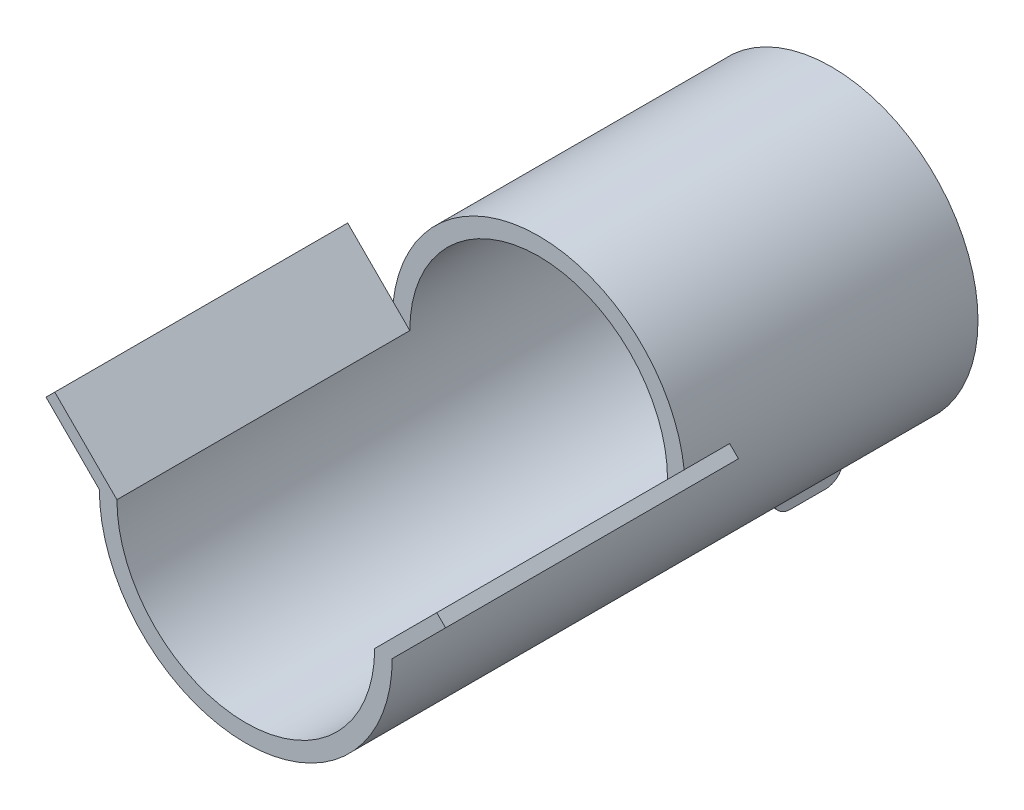
SolidWorks part; units mm, degrees
ref_plane "Front Plane" through (0, 0, 0) normal (0, 0, 1) x (1, 0, 0)
ref_plane "Top Plane" through (0, 0, 0) normal (0, 1, 0) x (1, 0, 0)
ref_plane "Right Plane" through (0, 0, 0) normal (1, 0, 0) x (0, 0, -1)
sketch "Sketch1" plane through (0, 0, 0) normal (0, 0, 1) x (1, 0, 0)
  circle A0 centre (0, 0) radius 25
  circle A1 centre (0, 0) radius 22
  dimension "D1" = 44
  dimension "D2" = 3
extrude "Boss-Extrude1" add sketch "Sketch1" along normal blind 100
sketch "Sketch2" plane through (0, 0, 0) normal (0, 0, -1) x (-1, 0, 0)
  line L1 (-5, 24.4949) -> (5, 24.4949)
  line L2 (-5, 24.4949) -> (-5, 14.4949)
  line L3 (-5, 14.4949) -> (5, 14.4949)
  line L4 (5, 24.4949) -> (5, 14.4949)
  line L5 (-5, 24.4949) -> (5, 14.4949) construction
  line L6 (-5, 14.4949) -> (5, 24.4949) construction
  circle A0 centre (0, 0) radius 25 construction
  point P0 (0, 19.4949)
  dimension "D1" = 10
  dimension "D2" = 10
extrude "Boss-Extrude3" add sketch "Sketch2" against normal blind 3
fillet "Fillet2" radius 3 3 edges at (0, 22, 3) (5, 21.4243, 1.5) (-5, 21.4243, 1.5)
fillet "Fillet3" radius 3 2 edges at (-5, 14.4949, 1.5) (5, 14.4949, 1.5)
sketch "Sketch3" plane through (0, 0, 0) normal (0, 0, -1) x (-1, 0, 0)
  line L1 (-2, -24.9199) -> (2, -24.9199)
  line L2 (-2, -24.9199) -> (-2, -34.9199)
  line L3 (-2, -34.9199) -> (2, -34.9199)
  line L4 (2, -24.9199) -> (2, -34.9199)
  line L5 (-2, -24.9199) -> (2, -34.9199) construction
  line L6 (-2, -34.9199) -> (2, -24.9199) construction
  circle A0 centre (0, 0) radius 25 construction
  point P0 (0, -29.9199)
  dimension "D1" = 4
  dimension "D2" = 10
extrude "Boss-Extrude4" add sketch "Sketch3" against normal blind 12
sketch "Sketch4" plane through (-2, 0, 0) normal (-1, 0, 0) x (0, 0, 1)
  circle A0 centre (5, -30.9199) radius 1.5
  dimension "D1" = 3
  dimension "D2" = 4
  dimension "D3" = 5
extrude "Cut-Extrude1" cut sketch "Sketch4" against normal up to next
fillet "Fillet4" radius 3 5 edges at (2, -24.9199, 6) (-2, -24.9199, 6) (0, -25, 12) (0, -34.9199, 12) (0, -34.9199, 0)
sketch "Sketch5" plane through (0, 0, 100) normal (0, 0, 1) x (1, 0, 0)
  line L1 (-31.6369, 26.2179) -> (31.6369, 26.2179)
  line L2 (-31.6369, 26.2179) -> (-31.6369, 0)
  line L3 (-31.6369, 0) -> (31.6369, 0)
  line L4 (31.6369, 26.2179) -> (31.6369, 0)
  line L5 (-31.6369, 26.2179) -> (31.6369, 0) construction
  line L6 (-31.6369, 0) -> (31.6369, 26.2179) construction
  point P0 (0, 13.1089)
extrude "Cut-Extrude2" cut sketch "Sketch5" against normal blind 50
sketch "Sketch8" plane through (0, 0, 100) normal (0, 0, 1) x (1, 0, 0)
  line L0 (25, 0) -> (22, 0)
  line L1 (22, 0) -> (32.6066, 10.6066)
  line L2 (32.6066, 10.6066) -> (34.1066, 9.1066)
  line L3 (34.1066, 9.1066) -> (25, 0)
  line L8 (-25, 0) -> (-22, 0)
  line L9 (-22, 0) -> (-32.6066, 10.6066)
  line L10 (-32.6066, 10.6066) -> (-34.1066, 9.1066)
  line L11 (-34.1066, 9.1066) -> (-25, 0)
  point P9 (0, 0)
  dimension "D1" = 45
  dimension "D2" = 45
  dimension "D3" = 15
extrude "Boss-Extrude5" add sketch "Sketch8" against normal up to surface (50 mm away) up to face at (0, 11.75, 50)
